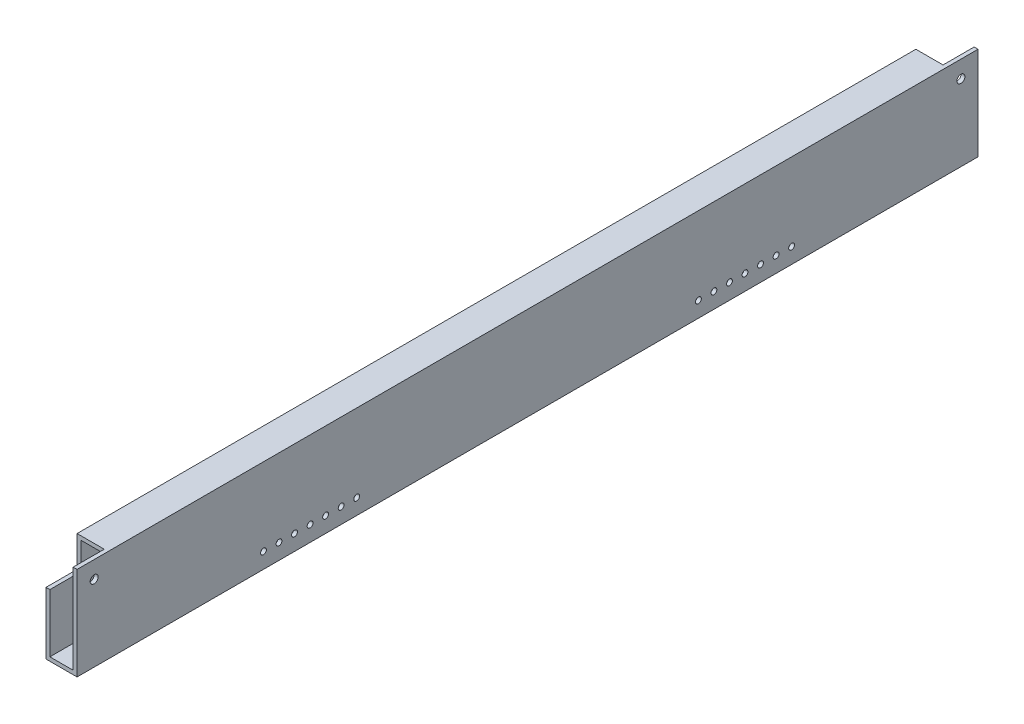
SolidWorks part; units mm, degrees
ref_plane "Front Plane" through (0, 0, 0) normal (0, 0, 1) x (1, 0, 0)
ref_plane "Top Plane" through (0, 0, 0) normal (0, 1, 0) x (1, 0, 0)
ref_plane "Right Plane" through (0, 0, 0) normal (1, 0, 0) x (0, 0, -1)
sketch "Sketch1" plane through (0, 0, 0) normal (0, 0, 1) x (1, 0, 0)
  line L1 (-12.7, -38.1) -> (12.7, -38.1)
  line L2 (-12.7, -38.1) -> (-12.7, 38.1)
  line L3 (-12.7, 38.1) -> (12.7, 38.1)
  line L4 (12.7, -38.1) -> (12.7, 38.1)
  line L5 (-12.7, -38.1) -> (12.7, 38.1) construction
  line L6 (-12.7, 38.1) -> (12.7, -38.1) construction
  point P0 (0, 0)
  dimension "D1" = 25.4
  dimension "D2" = 76.2
extrude "Boss-Extrude1" add sketch "Sketch1" along normal mid plane 736.6
shell "Shell1" thickness 3.175 removed face at (0, 0, -368.3) removed face at (0, 0, 368.3)
sketch "Sketch3" plane through (12.7, 0, 0) normal (1, 0, 0) x (0, 0, -1)
  line L0 (368.3, -38.1) -> (368.3, 38.1) construction
  line L1 (-368.3, -38.1) -> (368.3, -38.1) construction
  line L2 (0, -53.276) -> (0, 47.534) construction
  circle A0 centre (215.9, -25.4) radius 2.3813
  circle A1 centre (203.2, -25.4) radius 2.3813
  circle A2 centre (190.5, -25.4) radius 2.3813
  circle A3 centre (177.8, -25.4) radius 2.3813
  circle A4 centre (165.1, -25.4) radius 2.3813
  circle A5 centre (152.4, -25.4) radius 2.3813
  circle A6 centre (139.7, -25.4) radius 2.3813
  circle A7 centre (-139.7, -25.4) radius 2.3813
  circle A8 centre (-152.4, -25.4) radius 2.3813
  circle A9 centre (-165.1, -25.4) radius 2.3813
  circle A10 centre (-203.2, -25.4) radius 2.3813
  circle A11 centre (-177.8, -25.4) radius 2.3813
  circle A12 centre (-215.9, -25.4) radius 2.3813
  circle A13 centre (-190.5, -25.4) radius 2.3813
  dimension "D1" = 4.7625
  dimension "D3" = 12.7
  dimension "D4" = 12.7
  dimension "D5" = 12.7
  dimension "D6" = 12.7
  dimension "D7" = 12.7
  dimension "D8" = 12.7
  dimension "D9" = 12.7
  dimension "D10" = 12.7
  dimension "D2" = 152.4
extrude "Cut-Extrude2" cut sketch "Sketch3" against normal up to next
sketch "Sketch4" plane through (-12.7, 0, 0) normal (-1, 0, 0) x (0, 0, 1)
  line L1 (-368.3, 38.1) -> (-342.9, 38.1)
  line L2 (-368.3, 38.1) -> (-368.3, 12.7)
  line L3 (-368.3, 12.7) -> (-342.9, 12.7)
  line L4 (-342.9, 38.1) -> (-342.9, 12.7)
  line L5 (368.3, 38.1) -> (342.9, 38.1)
  line L6 (368.3, 38.1) -> (368.3, 12.7)
  line L7 (368.3, 12.7) -> (342.9, 12.7)
  line L8 (342.9, 38.1) -> (342.9, 12.7)
  dimension "D1" = 25.4
  dimension "D2" = 25.4
  dimension "D3" = 25.4
  dimension "D4" = 25.4
extrude "Cut-Extrude3" cut sketch "Sketch4" against normal blind 22.225
sketch "Sketch5" plane through (9.525, 0, 0) normal (-1, 0, 0) x (0, 0, 1)
  line L0 (-342.9, 38.1) -> (-368.3, 38.1) construction
  line L1 (-368.3, -34.925) -> (-368.3, 38.1) construction
  line L2 (368.3, 38.1) -> (342.9, 38.1) construction
  line L4 (368.3, -34.925) -> (368.3, 38.1) construction
  circle A0 centre (-354.33, 24.13) radius 3.25
  circle A1 centre (354.33, 24.13) radius 3.25
  dimension "D3" = 6.5
  dimension "D4" = 6.5
  dimension "D6" = 13.97
  dimension "D1" = 13.97
  dimension "D2" = 13.97
  dimension "D5" = 13.97
extrude "Cut-Extrude4" cut sketch "Sketch5" against normal blind 22.225
equation "\"robotwidth\"= 29in"
equation "\"D1@Boss-Extrude1\"=\"robotwidth\""
